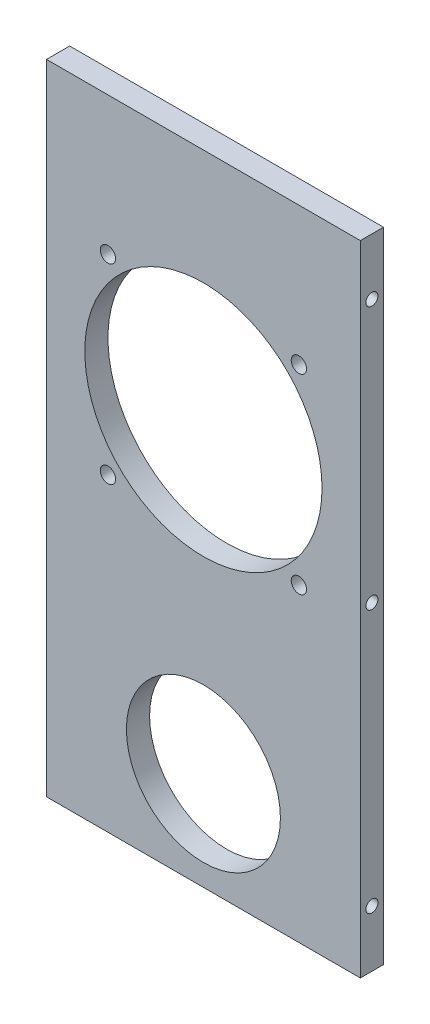
SolidWorks part; units mm, degrees
ref_plane "Front Plane" through (0, 0, 0) normal (0, 0, 1) x (1, 0, 0)
ref_plane "Top Plane" through (0, 0, 0) normal (0, 1, 0) x (1, 0, 0)
ref_plane "Right Plane" through (0, 0, 0) normal (1, 0, 0) x (0, 0, -1)
sketch "Sketch1" plane through (0, 0, 0) normal (0, 0, 1) x (1, 0, 0)
  line L1 (-43, -87.5) -> (43, -87.5)
  line L2 (-43, -87.5) -> (-43, 87.5)
  line L3 (-43, 87.5) -> (43, 87.5)
  line L4 (43, -87.5) -> (43, 87.5)
  line L5 (-43, -87.5) -> (43, 87.5) construction
  line L6 (-43, 87.5) -> (43, -87.5) construction
  point P0 (0, 0)
  dimension "D1" = 175
  dimension "D2" = 86
extrude "Boss-Extrude1" add sketch "Sketch1" along normal mid plane 6.35
sketch "Sketch3" plane through (-43, 0, 0) normal (-1, 0, 0) x (0, 0, 1)
  line L0 (0, 72) -> (0, -72) construction
  circle A0 centre (0, 72) radius 1.65
  circle A1 centre (0, 0) radius 1.65
  circle A2 centre (0, -72) radius 1.65
  point P4 (0, 0)
  point P8 (0, -72.1904)
  point P9 (0, -71.9604)
  dimension "D1" = 3.3
  dimension "D2" = 3.3
  dimension "D3" = 3.3
  dimension "D4" = 144
extrude "Cut-Extrude1" cut sketch "Sketch3" against normal blind 10 contours A2 | A1 | A0
mirror "Mirror1" about plane through (0, 0, 0) normal (1, 0, 0) of "Cut-Extrude1"
sketch "Sketch4" plane through (0, 0, 3.175) normal (0, 0, 1) x (1, 0, 0)
  line L0 (43, 87.5) -> (-43, 87.5) construction
  line L1 (-26.163, 49.663) -> (0, 23.5) construction
  line L2 (0, 23.5) -> (-37, 23.5) construction
  circle A0 centre (0, 23.5) radius 37 construction
  circle A1 centre (-26.163, 49.663) radius 2.1
  circle A2 centre (26.163, 49.663) radius 2.1
  circle A3 centre (26.163, -2.663) radius 2.1
  circle A4 centre (-26.163, -2.663) radius 2.1
  circle A5 centre (0, 23.5) radius 32.5
  dimension "D1" = 74
  dimension "D3" = 4.2
  dimension "D6" = 65
  dimension "D2" = 64
  dimension "D5" = 45
  dimension "D4" = 4
extrude "Cut-Extrude2" cut sketch "Sketch4" against normal through all contours A5
extrude "Cut-Extrude3" cut sketch "Sketch4<3>" against normal through all contours A1 | A4 | A3 | A2
sketch "Sketch4<3>" plane through (0, 0, 3.175) normal (0, 0, 1) x (1, 0, 0) same geometry as "Sketch4"
sketch "Sketch7" plane through (0, 0, 3.175) normal (0, 0, 1) x (1, 0, 0)
  circle A0 centre (0, -60.5) radius 21.1
  circle A1 centre (0, 23.5) radius 32.5 construction
  circle A2 centre (0, 23.5) radius 32.5
  point P2 (0, 0)
  point P7 (0, 0)
  point P8 (0, 0)
  dimension "D1" = 42.2
  dimension "D2" = 84
extrude "Cut-Extrude4" cut sketch "Sketch7" against normal through all contours A0
